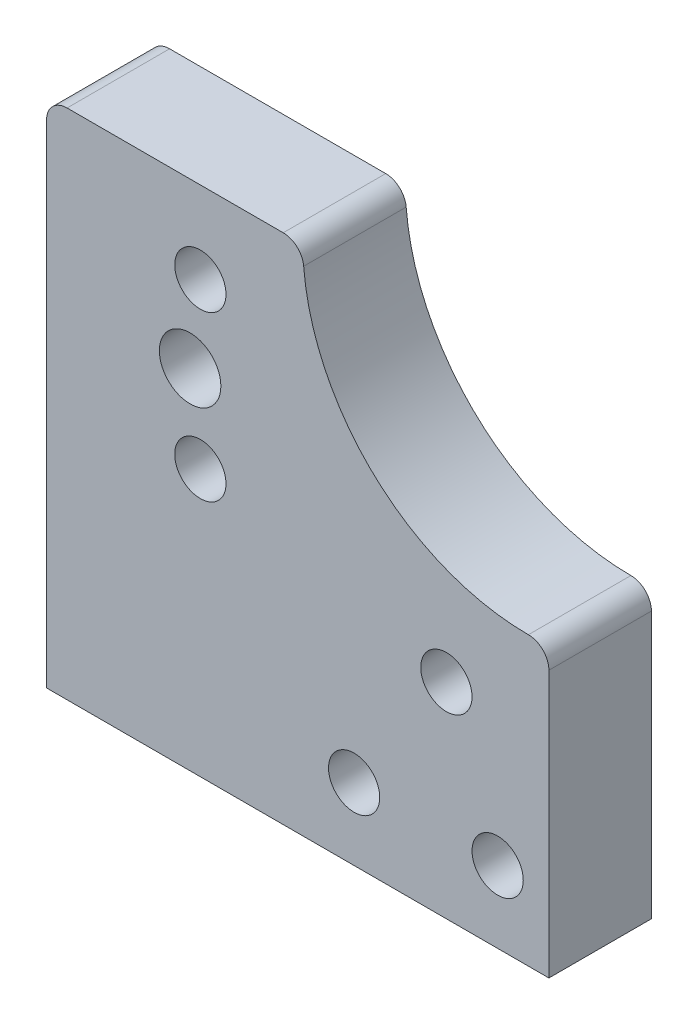
SolidWorks part; units mm, degrees
material "AISI 321 Annealed Stainless Steel (SS)"
ref_plane "Front Plane" through (0, 0, 0) normal (0, 0, 1) x (1, 0, 0)
ref_plane "Top Plane" through (0, 0, 0) normal (0, 1, 0) x (1, 0, 0)
ref_plane "Right Plane" through (0, 0, 0) normal (1, 0, 0) x (0, 0, -1)
sketch "Sketch1" plane through (0, 0, 0) normal (0, 0, 1) x (1, 0, 0)
  line L0 (-10, 25) -> (-2, 25)
  line L1 (10, 14) -> (10, 0.5)
  line L2 (55, 0) -> (-55, 0) construction
  line L3 (10, 0) -> (-10, 0)
  line L4 (-10, 0.5) -> (-10, 25) construction
  line L5 (0, -55) -> (0, 55) construction
  line L6 (-10, 0.5) -> (10, 0.5) construction
  line L7 (10, 0.5) -> (10, 0)
  line L8 (-10, 0) -> (-10, 0.5) construction
  line L9 (-10, 0) -> (-14.5, 0)
  line L10 (-14.5, 0) -> (-14.5, 25)
  line L11 (-14.5, 25) -> (-10, 25)
  line L12 (9, 14) -> (10, 14)
  circle A0 centre (-7.5, 17) radius 1.5
  arc A1 (-2, 25) -> (9, 14) centre (9, 25) ccw
  point P7 (0, 0)
  dimension "D3" = 3
  dimension "D1" = 20
  dimension "D2" = 25
  dimension "D4" = 17
  dimension "D5" = 2.5
  dimension "D6" = 0.5
  dimension "D7" = 4.5
  dimension "D8" = 14
  dimension "D9" = 8
extrude "Boss-Extrude1" add sketch "Sketch1" along normal blind 5
hole_wizard "Tap Drill for M3 Tap1" positions "Sketch2" profile "Sketch3" hole size "M3" standard "ISO" end condition through all
sketch "Sketch2" plane through (0, 0, 5) normal (0, 0, 1) x (1, 0, 0)
  line L3 (55, 0) -> (-55, 0) construction
  line L4 (-10, 0.5) -> (-10, 25) construction
  line L5 (-14.5, 0) -> (10, 0) construction
  line L6 (-14.5, 25) -> (-14.5, 0) construction
  circle A0 centre (-7.5, 17) radius 1.5 construction
  point P0 (-7, 13)
  point P2 (-7, 21)
  point P16 (5, 10)
  point P31 (0.5, 3.5)
  point P33 (7.5, 3.5)
  dimension "D4" = 7
  dimension "D1" = 8
  dimension "D2" = 13
  dimension "D3" = 3
  dimension "D5" = 12.5
  dimension "D6" = 7
  dimension "D7" = 3.5
  dimension "D8" = 15
sketch "Sketch3" plane through (-7, 13, 5) normal (1, 0, 0) x (0, -1, 0)
  line L0 (0, 0) -> (0, 5)
  line L1 (0, 5) -> (1.25, 5)
  line L2 (1.25, 5) -> (1.25, 0)
  line L5 (1.25, 0) -> (0, 0)
  line L11 (0, -6.35) -> (0, 107.95) construction
  dimension "Thru Hole Dia." = 2.5
  dimension "Thru Hole Depth" = 5
cosmetic thread "Cosmetic Thread1" parameters "D2"=3
cosmetic thread "Cosmetic Thread2" parameters "D2"=3
cosmetic thread "Cosmetic Thread3" parameters "D2"=3
cosmetic thread "Cosmetic Thread4" parameters "D2"=3
cosmetic thread "Cosmetic Thread5" parameters "D2"=3
sketch "Sketch4" plane through (0, 0, 5) normal (0, 0, 1) x (1, 0, 0)
  line L0 (-6.2, 5.5) -> (-3.7, 8)
  line L1 (-3.7, 8) -> (-2.2, 8)
  line L2 (-2.2, 8) -> (-2.2, 5.5)
  line L3 (-2.2, 5.5) -> (-6.2, 5.5)
  line L5 (10, 0) -> (10, 14) construction
  line L6 (-10, 0.5) -> (10, 0.5) construction
  dimension "D1" = 4
  dimension "D2" = 45
  dimension "D3" = 2.5
  dimension "D4" = 5
  dimension "D5" = 16.2
extrude "Boss-Extrude2" [suppressed] add sketch "Sketch4" along normal blind 3
hole_wizard "Tap Drill for M3 Tap2" positions "Sketch5" profile "Sketch6" hole size "M3" standard "ISO"
sketch "Sketch5" plane through (0, 0, 0) normal (0, -1, 0) x (-1, 0, 0)
  line L0 (14.5, -5) -> (14.5, 0) construction
  line L1 (10, 0) -> (14.5, 0) construction
  point P0 (3.75, -2.5)
  point P2 (10.25, -2.5)
  dimension "D1" = 6.5
  dimension "D2" = 4.25
  dimension "D3" = 2.5
sketch "Sketch6" plane through (-3.75, 0, 2.5) normal (1, 0, 0) x (0, 0, -1)
  line L0 (0, 0) -> (0, 4.7511)
  line L1 (0, 4.7511) -> (1.25, 4)
  line L2 (1.25, 4) -> (1.25, 0)
  line L5 (1.25, 0) -> (0, 0)
  line L10 (0, 4.7511) -> (-1.25, 4) construction
  line L11 (0, -6.35) -> (0, 107.95) construction
  dimension "Hole Dia." = 2.5
  dimension "Hole Depth" = 4
  dimension "Drill Angle" = 118
cosmetic thread "Cosmetic Thread6" parameters "D2"=3
cosmetic thread "Cosmetic Thread7" parameters "D2"=3
fillet "Fillet1" radius 1 3 edges at (-14.5, 25, 2.5) (-2, 25, 2.5) (10, 14, 2.5)
